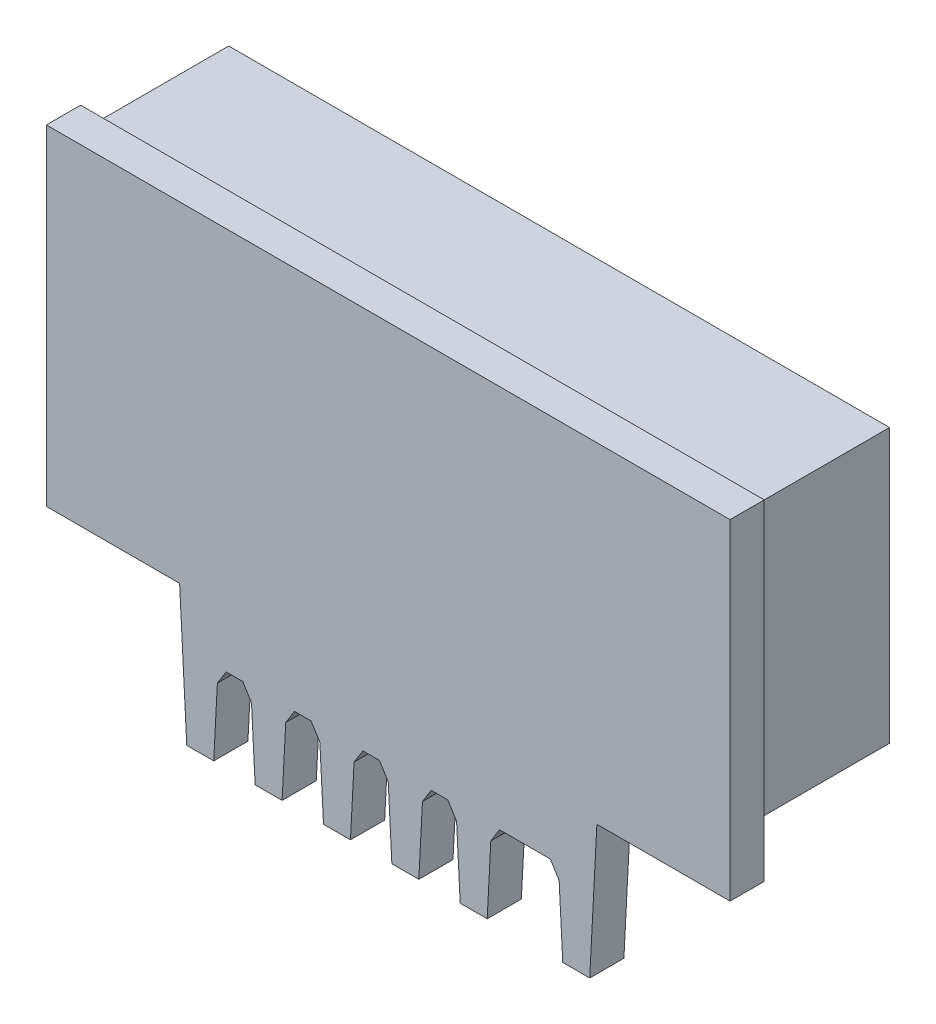
SolidWorks part; units mm, degrees
ref_plane "Front Plane" through (0, 0, 0) normal (0, 0, 1) x (1, 0, 0)
ref_plane "Top Plane" through (0, 0, 0) normal (0, 1, 0) x (1, 0, 0)
ref_plane "Right Plane" through (0, 0, 0) normal (1, 0, 0) x (0, 0, -1)
sketch "Sketch1" plane through (0, 0, 0) normal (0, 0, 1) x (1, 0, 0)
  line L0 (0, 0) -> (0, 20.5) construction
  line L1 (0, 20.5) -> (18.3124, 20.5) construction
  line L2 (18.3124, 20.5) -> (18.3124, 0) construction
  line L3 (18.3124, 0) -> (0, 0) construction
  line L4 (0, 3) -> (18.3124, 3) construction
  line L5 (0, 6) -> (18.3124, 6) construction
  line L6 (0.9062, 6) -> (0.9062, 0) construction
  line L7 (3.9062, 6) -> (3.9062, 0) construction
  line L8 (6.9062, 6) -> (6.9062, 0) construction
  line L9 (9.9062, 6) -> (9.9062, 0) construction
  line L10 (12.9062, 6) -> (12.9062, 0) construction
  line L11 (17.4062, 6) -> (17.4062, 0) construction
  line L12 (0.9062, 3) -> (3.9062, 3) construction
  line L13 (3.9062, 3) -> (6.9062, 3) construction
  line L14 (6.9062, 3) -> (9.9062, 3) construction
  line L15 (9.9062, 3) -> (12.9062, 3) construction
  line L16 (12.9062, 3) -> (17.4062, 3) construction
  line L17 (0.9062, 3) -> (0, 3) construction
  line L18 (17.4062, 3) -> (18.3124, 3) construction
  line L19 (2.4062, 3) -> (2.4062, 0) construction
  line L20 (5.4062, 3) -> (5.4062, 0) construction
  line L21 (8.4062, 3) -> (8.4062, 0) construction
  line L22 (11.4062, 3) -> (11.4062, 0) construction
  line L23 (15.1562, 3) -> (15.1562, 0) construction
  line L24 (14.4062, 3.75) -> (15.9062, 3.75) construction
  line L25 (0, 6) -> (0.3144, 0)
  line L26 (0.3144, 0) -> (1.4979, 0)
  line L27 (1.4979, 0) -> (1.6572, 3.0393)
  line L28 (3.1552, 3.0393) -> (3.3144, 0)
  line L29 (3.3144, 0) -> (4.4979, 0)
  line L30 (4.4979, 0) -> (4.6572, 3.0393)
  line L31 (6.1552, 3.0393) -> (6.3144, 0)
  line L32 (6.3144, 0) -> (7.4979, 0)
  line L33 (7.4979, 0) -> (7.6572, 3.0393)
  line L34 (9.1552, 3.0393) -> (9.3144, 0)
  line L35 (9.3144, 0) -> (10.4979, 0)
  line L36 (10.4979, 0) -> (10.6572, 3.0393)
  line L37 (12.1552, 3.0393) -> (12.3144, 0)
  line L38 (12.3144, 0) -> (13.4979, 0)
  line L39 (13.4979, 0) -> (13.6572, 3.0393)
  line L40 (16.6552, 3.0393) -> (16.8144, 0)
  line L41 (16.8144, 0) -> (17.9979, 0)
  line L42 (17.9979, 0) -> (18.3124, 6)
  line L44 (1.6572, 3.0393) -> (2.0426, 3.656)
  line L45 (0, 6) -> (-5.8438, 6)
  line L46 (-5.8438, 20.5) -> (24.1562, 20.5)
  line L47 (-5.8438, 6) -> (-5.8438, 20.5)
  line L48 (9.1562, 20.5) -> (9.1562, 6) construction
  line L49 (2.0426, 3.656) -> (2.7698, 3.656)
  line L50 (2.7698, 3.656) -> (3.1552, 3.0393)
  line L51 (4.6572, 3.0393) -> (5.0426, 3.656)
  line L52 (5.0426, 3.656) -> (5.7698, 3.656)
  line L53 (5.7698, 3.656) -> (6.1552, 3.0393)
  line L54 (7.6572, 3.0393) -> (8.0426, 3.656)
  line L55 (8.0426, 3.656) -> (8.7698, 3.656)
  line L56 (8.7698, 3.656) -> (9.1552, 3.0393)
  line L57 (10.6572, 3.0393) -> (11.0426, 3.656)
  line L58 (11.0426, 3.656) -> (11.7698, 3.656)
  line L59 (11.7698, 3.656) -> (12.1552, 3.0393)
  line L60 (13.6572, 3.0393) -> (14.0426, 3.656)
  line L61 (14.0426, 3.656) -> (16.2698, 3.656)
  line L62 (16.2698, 3.656) -> (16.6552, 3.0393)
  line L63 (18.3124, 6) -> (24.1562, 6)
  line L64 (24.1562, 6) -> (24.1562, 20.5)
  line L65 (24.1562, 20.5) -> (24.1562, 21) construction
  line L66 (23.6562, 20) -> (-5.3438, 20) construction
  line L67 (23.6562, 20) -> (23.6562, 8) construction
  line L68 (23.6562, 8) -> (-5.3438, 8) construction
  line L69 (-5.3438, 20) -> (-5.3438, 8) construction
  line L70 (24.1562, 21) -> (-5.8438, 21) construction
  line L71 (-5.8438, 21) -> (-5.8438, 20.5) construction
  arc A0 (3.1552, 3.0393) -> (1.6572, 3.0393) centre (2.4062, 3) ccw construction
  arc A1 (6.1552, 3.0393) -> (4.6572, 3.0393) centre (5.4062, 3) ccw construction
  arc A2 (9.1552, 3.0393) -> (7.6572, 3.0393) centre (8.4062, 3) ccw construction
  arc A3 (12.1552, 3.0393) -> (10.6572, 3.0393) centre (11.4062, 3) ccw construction
  arc A4 (13.6572, 3.0393) -> (14.4062, 3.75) centre (14.4062, 3) cw construction
  arc A5 (16.6552, 3.0393) -> (15.9062, 3.75) centre (15.9062, 3) ccw construction
  dimension "D7" = 0.75
  dimension "D16" = 0.5
  dimension "D11" = 2
  dimension "D1" = 3
  dimension "D2" = 6
  dimension "D3" = 12
  dimension "D4" = 3
  dimension "D5" = 30
  dimension "D6" = 4.5
  dimension "D8" = 3
  dimension "D9" = 18.3124
  dimension "D10" = 20.5
  dimension "D12" = 14.5
  dimension "D13" = 0.5
  dimension "D14" = 0.5
  dimension "D15" = 29
extrude "Boss-Extrude1" add sketch "Sketch1" along normal blind 1.5
sketch "Sketch3" plane through (0, 0, 0) normal (0, 0, 1) x (1, 0, 0)
  line L0 (-0.4005, 6) -> (18.7129, 6)
  line L1 (18.7129, 3) -> (-0.4005, 3) construction
  line L2 (-0.4005, 0) -> (18.7129, 0) construction
  line L3 (-0.4005, -0.5) -> (18.7129, -0.5) construction
  line L4 (18.7129, -0.5) -> (18.7129, 6) construction
  line L5 (-0.4005, 6) -> (-0.4005, -0.5) construction
  line L6 (18.3124, 0) -> (0, 0) construction
  line L7 (0, 3) -> (18.3124, 3) construction
  line L8 (0, 6) -> (18.3124, 6) construction
  line L9 (0.3407, -0.5) -> (0, 6) construction
  line L10 (18.3124, 6) -> (17.9717, -0.5) construction
  line L11 (17.9979, 0) -> (18.3124, 6) construction
  line L12 (0, 6) -> (0.3144, 0) construction
  line L13 (5.4062, 6) -> (5.4062, -0.5) construction
  line L14 (3.9062, 6) -> (3.9062, -0.5) construction
  line L15 (5.4062, 3) -> (5.4062, 0) construction
  line L16 (3.1572, 3) -> (3.3407, -0.5) construction
  line L17 (2.7567, 3) -> (2.9401, -0.5)
  line L18 (3.1552, 3.0393) -> (3.3144, 0) construction
  line L19 (2.9401, -0.5) -> (4.8723, -0.5)
  line L20 (4.8723, -0.5) -> (5.0557, 3)
  line L21 (2.8484, 1.25) -> (3.2478, 1.2709) construction
  line L22 (5.9401, -0.5) -> (5.7567, 3)
  line L26 (7.8723, -0.5) -> (5.9401, -0.5)
  line L27 (8.0557, 3) -> (7.8723, -0.5)
  line L30 (2.4062, -0.5) -> (2.4062, 6) construction
  line L31 (2.4062, 3) -> (2.4062, 0) construction
  line L32 (8.4062, 6) -> (8.4062, -0.5) construction
  line L34 (11.4062, -0.5) -> (11.4062, 6) construction
  line L35 (15.1562, -0.5) -> (15.1562, 6) construction
  line L36 (8.4062, 3) -> (8.4062, 0) construction
  line L37 (11.4062, 3) -> (11.4062, 0) construction
  line L38 (15.1562, 3) -> (15.1562, 0) construction
  line L39 (10.8723, -0.5) -> (11.0557, 3)
  line L40 (8.9401, -0.5) -> (10.8723, -0.5)
  line L41 (8.7567, 3) -> (8.9401, -0.5)
  line L42 (11.9401, -0.5) -> (11.7567, 3)
  line L43 (13.8723, -0.5) -> (11.9401, -0.5)
  line L44 (14.0557, 3) -> (13.8723, -0.5)
  line L45 (16.4401, -0.5) -> (18.3723, -0.5)
  line L46 (16.2567, 3) -> (16.4401, -0.5)
  line L47 (18.3723, -0.5) -> (18.7129, 6)
  line L48 (1.8723, -0.5) -> (-0.0599, -0.5)
  line L49 (2.0557, 3) -> (1.8723, -0.5)
  line L50 (-0.0599, -0.5) -> (-0.4005, 6)
  line L51 (16.2567, 3) -> (14.0557, 3)
  line L52 (11.7567, 3) -> (11.0557, 3)
  line L53 (8.7567, 3) -> (8.0557, 3)
  line L54 (5.7567, 3) -> (5.0557, 3)
  line L55 (2.7567, 3) -> (2.0557, 3)
  dimension "D1" = 0.5
  dimension "D2" = 0.4
ref_plane "Plane1" through (3.9062, 0, 0) normal (1, 0, 0) x (0, 0, -1)
sketch "Sketch4" plane through (3.9062, 0, 0) normal (1, 0, 0) x (0, 0, -1)
  line L0 (0, 6) -> (0, -0.5) construction
  line L1 (0.6, 6) -> (-2.1, 6) construction
  line L2 (0.6, 6) -> (0.6, -0.5) construction
  line L3 (0.6, -0.5) -> (-2.1, -0.5) construction
  line L4 (-2.1, 6) -> (-2.1, -0.5) construction
  line L5 (-0.75, -0.5) -> (-0.75, 6) construction
  line L6 (-1.5, 6) -> (-1.5, -0.5) construction
  line L7 (0.6, 2.4005) -> (-2.1, 2.4005) construction
  line L8 (0.3, 6) -> (0.3, -0.5) construction
  line L9 (0.6, 2.4005) -> (3.846, 6) construction
  line L10 (2.2302, 6) -> (0.6, 4.1923) construction
  line L11 (0.6, 4.1923) -> (1.7139, 3.1878) construction
  line L12 (1.7139, 3.1878) -> (4.25, 6)
  line L13 (4.25, 6) -> (0.6, 6) construction
  line L14 (0.3, 1) -> (-1.8, 1) construction
  line L15 (-2.1, 0) -> (0.6, 0) construction
  line L16 (1.7139, 3.1878) -> (1.4912, 3.3887)
  line L17 (1.4912, 3.3887) -> (0.6, 2.4005)
  line L18 (-3.2139, 3.1878) -> (-5.75, 6)
  line L19 (-3.2139, 3.1878) -> (-2.9912, 3.3887)
  line L20 (-2.9912, 3.3887) -> (-2.1, 2.4005)
  line L21 (-2.1, 6) -> (-5.75, 6) construction
  line L22 (0.6, 3.0724) -> (3.2401, 6) construction
  arc A0 (0.4965, 2.2224) -> (0.6, -0.5) centre (4.2, 1) ccw
  arc A1 (0.6, 2.4005) -> (0.4965, 2.2224) centre (0.9713, 2.0656) ccw
  arc A2 (-2.1, 2.4005) -> (-1.9965, 2.2224) centre (-2.4713, 2.0656) cw
  arc A3 (-1.9965, 2.2224) -> (-2.1, -0.5) centre (-5.7, 1) cw
  dimension "D6" = 0.5
  dimension "D1" = 0.6
  dimension "D2" = 0.3
  dimension "D3" = 1.5
  dimension "D4" = 1
  dimension "D5" = 0.3
  dimension "D7" = 10
sketch "Sketch5" plane through (0, 0, 0) normal (1, 0, 0) x (0, 0, -1)
  line L0 (2.2302, 6) -> (0.6, 4.1923) construction
  line L1 (0.6, 4.1923) -> (1.7139, 3.1878) construction
  line L2 (1.7139, 3.1878) -> (4.25, 6) construction
  line L3 (2.2302, 6) -> (0.6, 4.1923) construction
  line L4 (0.6, 4.1923) -> (1.7139, 3.1878) construction
  line L5 (1.7139, 3.1878) -> (4.25, 6) construction
ref_plane "Plane2" through (0, 2.6105, -2.3541) normal (0, 0.7426, -0.6697) x (1, 0, 0)
sketch "Sketch6" plane through (0, 2.6105, -2.3541) normal (0, 0.7426, -0.6697) x (1, 0, 0)
  line L1 (3.9062, -2.362) -> (3.9062, -0.862) construction
  line L2 (3.9062, -2.362) -> (3.9062, -5.0612) construction
  line L3 (4.6562, -5.0612) -> (3.1562, -5.0612)
  line L4 (4.6562, -1.612) -> (3.1562, -1.612) construction
  line L5 (3.1562, -1.612) -> (3.1562, -5.0612)
  line L6 (4.6562, -1.612) -> (4.6562, -5.0612)
  line L10 (2.4062, -5.0612) -> (15.1562, -5.0612) construction
  line L11 (15.1562, -5.0612) -> (15.1562, -0.862) construction
  line L12 (15.1562, -0.862) -> (2.4062, -0.862) construction
  line L13 (2.4062, -0.862) -> (2.4062, -5.0612) construction
  line L14 (15.1562, 0.3349) -> (15.1562, -4.0182) construction
  line L15 (2.4062, 0.3349) -> (2.4062, -4.0182) construction
  line L16 (11.4062, -5.0612) -> (11.4062, -0.862) construction
  line L17 (8.4062, -5.0612) -> (8.4062, -0.862) construction
  line L18 (5.4062, -5.0612) -> (5.4062, -0.862) construction
  line L19 (5.4062, -4.0182) -> (5.4062, 0.3349) construction
  line L20 (8.4062, -4.0182) -> (8.4062, 0.3349) construction
  line L21 (11.4062, 0.3349) -> (11.4062, -4.0182) construction
  line L22 (0.1562, -1.612) -> (0.1562, -5.0612)
  line L23 (0.1562, -5.0612) -> (1.6562, -5.0612)
  line L24 (1.6562, -1.612) -> (1.6562, -5.0612)
  line L25 (7.6562, -1.612) -> (7.6562, -5.0612)
  line L26 (6.1562, -5.0612) -> (7.6562, -5.0612)
  line L27 (6.1562, -1.612) -> (6.1562, -5.0612)
  line L28 (10.6562, -1.612) -> (10.6562, -5.0612)
  line L29 (10.6562, -5.0612) -> (9.1562, -5.0612)
  line L30 (9.1562, -1.612) -> (9.1562, -5.0612)
  line L31 (13.6562, -1.612) -> (13.6562, -5.0612)
  line L32 (12.1562, -5.0612) -> (13.6562, -5.0612)
  line L33 (12.1562, -1.612) -> (12.1562, -5.0612)
  line L34 (18.1562, -1.612) -> (18.1562, -5.0612)
  line L35 (18.1562, -5.0612) -> (16.6562, -5.0612)
  line L36 (16.6562, -1.612) -> (16.6562, -5.0612)
  circle A0 centre (3.9062, -1.612) radius 0.75 construction
  arc A1 (4.6562, -1.612) -> (3.1562, -1.612) centre (3.9062, -1.612) ccw
  arc A2 (0.1562, -1.612) -> (1.6562, -1.612) centre (0.9062, -1.612) cw
  arc A3 (6.1562, -1.612) -> (7.6562, -1.612) centre (6.9062, -1.612) cw
  arc A4 (10.6562, -1.612) -> (9.1562, -1.612) centre (9.9062, -1.612) ccw
  arc A5 (12.1562, -1.612) -> (13.6562, -1.612) centre (12.9062, -1.612) cw
  arc A6 (18.1562, -1.612) -> (16.6562, -1.612) centre (17.4062, -1.612) ccw
ref_plane "Plane3" through (0, 1.6223, -1.463) normal (0, 0.7426, -0.6697) x (1, 0, 0)
sketch "Sketch7" plane through (0, 1.6223, -1.463) normal (0, 0.7426, -0.6697) x (1, 0, 0)
  line L0 (3.1562, -1.612) -> (3.1562, -5.0612) construction
  line L1 (4.6562, -5.0612) -> (3.1562, -5.0612) construction
  line L2 (4.6562, -1.612) -> (4.6562, -5.0612) construction
  line L3 (3.1562, -1.612) -> (3.1562, -5.0612) construction
  line L4 (4.6562, -5.0612) -> (3.1562, -5.0612) construction
  line L5 (4.6562, -1.612) -> (4.6562, -5.0612) construction
  line L6 (3.9062, -0.862) -> (3.9062, -5.0612) construction
  line L7 (4.6562, -1.612) -> (3.1562, -1.612) construction
  line L8 (4.6562, -2.362) -> (3.1562, -2.362) construction
  line L9 (3.4562, -1.612) -> (3.4562, -2.362)
  line L10 (3.4562, -2.362) -> (4.3562, -2.362)
  line L11 (4.3562, -2.362) -> (4.3562, -1.612)
  line L12 (2.4062, -0.862) -> (2.4062, -5.0612) construction
  line L13 (2.4062, -5.0612) -> (15.1562, -5.0612) construction
  line L14 (15.1562, -0.862) -> (2.4062, -0.862) construction
  line L15 (5.4062, -5.0612) -> (5.4062, -0.862) construction
  line L16 (8.4062, -5.0612) -> (8.4062, -0.862) construction
  line L17 (11.4062, -5.0612) -> (11.4062, -0.862) construction
  line L18 (15.1562, -5.0612) -> (15.1562, -0.862) construction
  line L19 (2.4062, -0.862) -> (2.4062, -5.0612) construction
  line L20 (2.4062, -5.0612) -> (15.1562, -5.0612) construction
  line L21 (15.1562, -0.862) -> (2.4062, -0.862) construction
  line L22 (5.4062, -5.0612) -> (5.4062, -0.862) construction
  line L23 (8.4062, -5.0612) -> (8.4062, -0.862) construction
  line L24 (11.4062, -5.0612) -> (11.4062, -0.862) construction
  line L25 (15.1562, -5.0612) -> (15.1562, -0.862) construction
  line L26 (0.4562, -2.362) -> (0.4562, -1.612)
  line L27 (1.3562, -2.362) -> (0.4562, -2.362)
  line L28 (1.3562, -1.612) -> (1.3562, -2.362)
  line L29 (7.3562, -2.362) -> (6.4562, -2.362)
  line L30 (7.3562, -1.612) -> (7.3562, -2.362)
  line L31 (6.4562, -2.362) -> (6.4562, -1.612)
  line L32 (9.4562, -1.612) -> (9.4562, -2.362)
  line L33 (10.3562, -2.362) -> (10.3562, -1.612)
  line L34 (9.4562, -2.362) -> (10.3562, -2.362)
  line L35 (13.3562, -1.612) -> (13.3562, -2.362)
  line L36 (12.4562, -2.362) -> (12.4562, -1.612)
  line L37 (13.3562, -2.362) -> (12.4562, -2.362)
  line L38 (16.9562, -1.612) -> (16.9562, -2.362)
  line L39 (17.8562, -2.362) -> (17.8562, -1.612)
  line L40 (16.9562, -2.362) -> (17.8562, -2.362)
  arc A0 (4.6562, -1.612) -> (3.1562, -1.612) centre (3.9062, -1.612) ccw construction
  arc A1 (4.6562, -1.612) -> (3.1562, -1.612) centre (3.9062, -1.612) ccw construction
  circle A2 centre (3.9062, -1.612) radius 0.45 construction
  arc A3 (4.3562, -1.612) -> (3.4562, -1.612) centre (3.9062, -1.612) ccw
  arc A4 (0.4562, -1.612) -> (1.3562, -1.612) centre (0.9062, -1.612) cw
  arc A5 (6.4562, -1.612) -> (7.3562, -1.612) centre (6.9062, -1.612) cw
  arc A6 (10.3562, -1.612) -> (9.4562, -1.612) centre (9.9062, -1.612) ccw
  arc A7 (12.4562, -1.612) -> (13.3562, -1.612) centre (12.9062, -1.612) cw
  arc A8 (17.8562, -1.612) -> (16.9562, -1.612) centre (17.4062, -1.612) ccw
ref_plane "bisect" through (0, 0, 0.75) normal (0, 0, 1) x (1, 0, 0)
ref_plane "insert_surface" through (0, 6, 0) normal (0, 1, 0) x (1, 0, 0)
sketch "Sketch8" plane through (0, 6, 0) normal (0, 1, 0) x (1, 0, 0)
  line L0 (18.7129, -0.75) -> (-0.4005, -0.75) construction
  line L1 (-0.4005, 0.6) -> (18.7129, 0.6)
  line L2 (-0.4005, 0.6) -> (-0.4005, -2.1)
  line L3 (-0.4005, -2.1) -> (18.7129, -2.1)
  line L4 (18.7129, 0.6) -> (18.7129, -2.1)
  line L5 (9.1562, 0.6) -> (9.1562, -2.1) construction
  line L6 (0, 0) -> (18.3124, 0) construction
  line L7 (0, 0) -> (0, -1.5) construction
  line L8 (0, -1.5) -> (18.3124, -1.5) construction
  line L9 (18.3124, 0) -> (18.3124, -1.5) construction
  line L10 (18.7129, 0.3) -> (-0.4005, 0.3) construction
  line L11 (18.7129, -1.8) -> (-0.4005, -1.8) construction
sketch "Sketch9" plane through (0, 0, 0) normal (0, 0, 1) x (1, 0, 0)
  line L0 (18.3723, -0.5) -> (18.7129, 6) construction
  line L1 (-0.4005, 6) -> (18.7129, 6) construction
  line L2 (-0.0599, -0.5) -> (-0.4005, 6) construction
  line L3 (1.8723, -0.5) -> (-0.0599, -0.5) construction
  line L4 (2.0557, 3) -> (1.8723, -0.5) construction
  line L5 (2.7567, 3) -> (2.0557, 3) construction
  line L6 (2.7567, 3) -> (2.9401, -0.5) construction
  line L7 (2.9401, -0.5) -> (4.8723, -0.5) construction
  line L8 (4.8723, -0.5) -> (5.0557, 3) construction
  line L9 (5.7567, 3) -> (5.0557, 3) construction
  line L10 (5.9401, -0.5) -> (5.7567, 3) construction
  line L11 (7.8723, -0.5) -> (5.9401, -0.5) construction
  line L12 (8.0557, 3) -> (7.8723, -0.5) construction
  line L13 (8.7567, 3) -> (8.0557, 3) construction
  line L14 (8.7567, 3) -> (8.9401, -0.5) construction
  line L15 (8.9401, -0.5) -> (10.8723, -0.5) construction
  line L16 (10.8723, -0.5) -> (11.0557, 3) construction
  line L17 (11.7567, 3) -> (11.0557, 3) construction
  line L18 (11.9401, -0.5) -> (11.7567, 3) construction
  line L19 (13.8723, -0.5) -> (11.9401, -0.5) construction
  line L20 (14.0557, 3) -> (13.8723, -0.5) construction
  line L21 (16.2567, 3) -> (14.0557, 3) construction
  line L22 (16.2567, 3) -> (16.4401, -0.5) construction
  line L23 (16.4401, -0.5) -> (18.3723, -0.5) construction
  line L24 (18.3723, -0.5) -> (18.7129, 6)
  line L25 (-0.4005, 6) -> (18.7129, 6) construction
  line L26 (-0.0599, -0.5) -> (-0.4005, 6)
  line L27 (1.8723, -0.5) -> (-0.0599, -0.5)
  line L28 (2.0557, 3) -> (1.8723, -0.5)
  line L29 (2.7567, 3) -> (2.0557, 3) construction
  line L30 (2.7567, 3) -> (2.9401, -0.5)
  line L31 (2.9401, -0.5) -> (4.8723, -0.5)
  line L32 (4.8723, -0.5) -> (5.0557, 3)
  line L33 (5.7567, 3) -> (5.0557, 3) construction
  line L34 (5.9401, -0.5) -> (5.7567, 3)
  line L35 (7.8723, -0.5) -> (5.9401, -0.5)
  line L36 (8.0557, 3) -> (7.8723, -0.5)
  line L37 (8.7567, 3) -> (8.0557, 3) construction
  line L38 (8.7567, 3) -> (8.9401, -0.5)
  line L39 (8.9401, -0.5) -> (10.8723, -0.5)
  line L40 (10.8723, -0.5) -> (11.0557, 3)
  line L41 (11.7567, 3) -> (11.0557, 3) construction
  line L42 (11.9401, -0.5) -> (11.7567, 3)
  line L43 (13.8723, -0.5) -> (11.9401, -0.5)
  line L44 (14.0557, 3) -> (13.8723, -0.5)
  line L45 (16.2567, 3) -> (14.0557, 3) construction
  line L46 (16.2567, 3) -> (16.4401, -0.5)
  line L47 (16.4401, -0.5) -> (18.3723, -0.5)
  line L48 (16.2567, 3) -> (16.2567, 6)
  line L49 (14.0557, 3) -> (14.0557, 6)
  line L50 (11.7567, 3) -> (11.7567, 6)
  line L51 (18.7129, 6) -> (-0.4005, 6) construction
  line L52 (11.0557, 3) -> (11.0557, 6)
  line L53 (-0.4005, 6) -> (18.7129, 6) construction
  line L54 (8.7567, 3) -> (8.7567, 6)
  line L55 (8.0557, 3) -> (8.0557, 6)
  line L58 (5.7567, 3) -> (5.7567, 6)
  line L60 (5.0557, 3) -> (5.0557, 6)
  line L62 (15.1562, -0.5) -> (15.1562, 6) construction
  line L63 (15.1562, -0.5) -> (15.1562, 6) construction
  line L64 (2.7567, 3) -> (2.7567, 6)
  line L65 (2.0557, 3) -> (2.0557, 6)
  line L67 (18.7129, 6) -> (16.2567, 6)
  line L68 (14.0557, 6) -> (11.7567, 6)
  line L69 (11.0557, 6) -> (8.7567, 6)
  line L70 (8.0557, 6) -> (5.7567, 6)
  line L71 (5.0557, 6) -> (2.7567, 6)
  line L72 (2.0557, 6) -> (-0.4005, 6)
sketch "Sketch11" plane through (0, 6, 0) normal (0, 1, 0) x (1, 0, 0)
  line L0 (9.1562, -0.75) -> (9.1562, -2.1) construction
  line L1 (-0.3988, 0.6) -> (18.7112, 0.6)
  line L2 (-0.3988, 0.6) -> (-0.3988, -2.1)
  line L3 (-0.3988, -2.1) -> (18.7112, -2.1)
  line L4 (18.7112, 0.6) -> (18.7112, -2.1)
  line L5 (9.1562, -0.75) -> (9.1562, 0.6) construction
  line L6 (9.1562, -0.75) -> (18.7112, -0.75) construction
  line L7 (9.1562, -0.75) -> (-0.3988, -0.75) construction
  line L8 (-10.5124, -0.75) -> (10.5124, -0.75) construction
  dimension "D1" = 2.7
  dimension "D2" = 19.11
sketch "Sketch12" plane through (0, 0, 0) normal (0, 0, 1) x (1, 0, 0)
  line L0 (-5.3438, 20) -> (-5.3438, 8)
  line L1 (-5.3438, 8) -> (23.6562, 8)
  line L2 (23.6562, 8) -> (23.6562, 20)
  line L3 (23.6562, 20) -> (-5.3438, 20)
  line L4 (23.6562, 8) -> (-5.3438, 8) construction
  line L8 (23.6562, 20) -> (-5.3438, 20) construction
  line L9 (-5.3438, 20) -> (-5.3438, 8) construction
  line L10 (23.6562, 20) -> (23.6562, 8) construction
extrude "Boss-Extrude2" add sketch "Sketch12" against normal blind 6
ref_plane "right_center" through (9.1562, 0, 0) normal (1, 0, 0) x (0, 0, -1)
ref_plane "clear_plane" through (0, 21, 0) normal (0, 1, 0) x (1, 0, 0)
sketch "Sketch14" plane through (0, 21, 0) normal (0, 1, 0) x (1, 0, 0)
  line L0 (-6.3438, 0.5) -> (-6.3438, -2)
  line L1 (-6.3438, -2) -> (24.6562, -2)
  line L2 (24.6562, -2) -> (24.6562, 0.5)
  line L3 (24.6562, 0.5) -> (-6.3438, 0.5)
  line L4 (24.1562, 0) -> (-5.8438, 0)
  line L5 (-5.8438, 0) -> (-5.8438, -1.5)
  line L6 (-5.8438, -1.5) -> (24.1562, -1.5)
  line L7 (24.1562, -1.5) -> (24.1562, 0)
  line L8 (24.1562, 0) -> (-5.8438, 0) construction
  line L9 (-5.8438, 0) -> (-5.8438, -1.5) construction
  line L10 (-5.8438, -1.5) -> (24.1562, -1.5) construction
  line L11 (24.1562, -1.5) -> (24.1562, 0) construction
  dimension "D1" = 0
  dimension "D2" = 0.5
